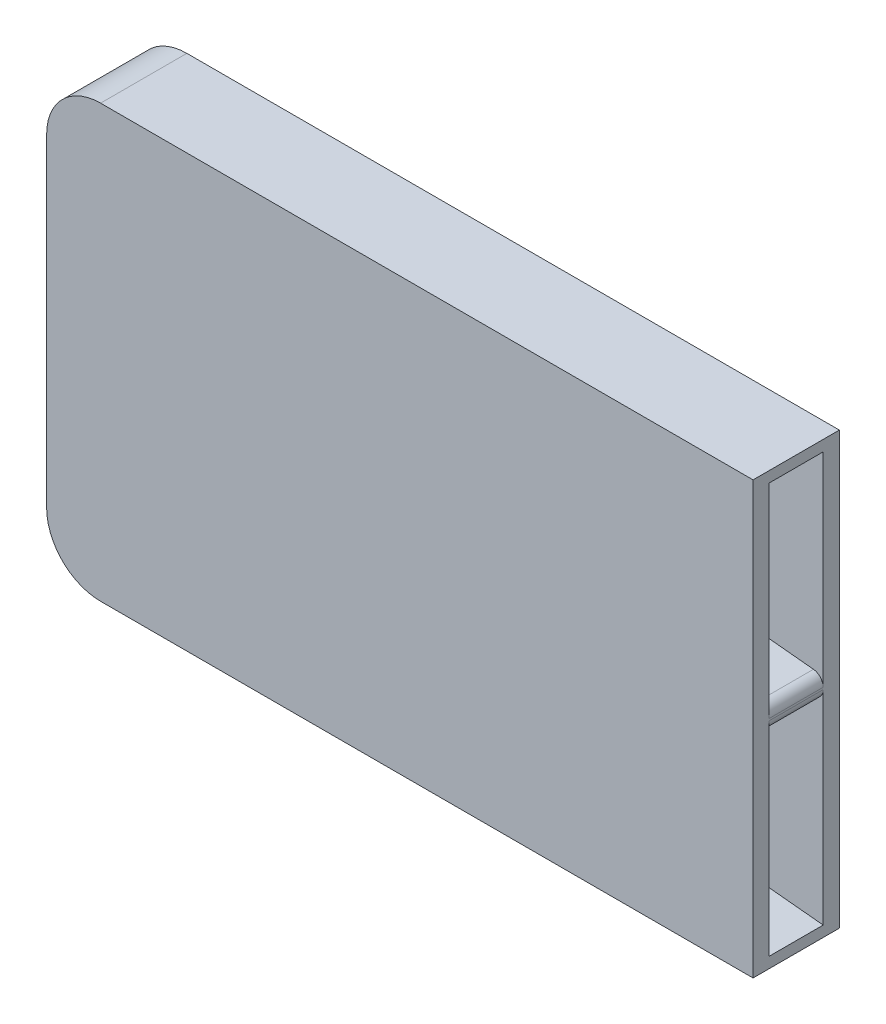
SolidWorks part; units mm, degrees
material "ABS"
ref_plane "Front Plane" through (0, 0, 0) normal (0, 0, 1) x (1, 0, 0)
ref_plane "Top Plane" through (0, 0, 0) normal (0, 1, 0) x (1, 0, 0)
ref_plane "Right Plane" through (0, 0, 0) normal (1, 0, 0) x (0, 0, -1)
sketch "Sketch1" plane through (0, 0, 0) normal (0, 0, 1) x (1, 0, 0)
  line L0 (0, 0) -> (0, 40)
  line L1 (0, 40) -> (65.5, 40)
  line L2 (65.5, 40) -> (65.5, 0)
  line L3 (65.5, 0) -> (0, 0)
  line L4 (65.5, 20) -> (0, 20) construction
  line L5 (0, 7.5) -> (65.5, 1)
  line L6 (0, 12.5) -> (65.5, 19)
  line L7 (0, 10) -> (65.5, 10) construction
  line L8 (0, 32.5) -> (65.5, 39)
  line L9 (0, 30) -> (65.5, 30) construction
  line L10 (0, 27.5) -> (65.5, 21)
  dimension "D1" = 40
  dimension "D2" = 5
  dimension "D3" = 18
  dimension "D4" = 20
  dimension "D5" = 65.5
extrude "Boss-Extrude1" add sketch "Sketch1" against normal blind 1.5 contours L0 L8 L2 L1 | L0 L10 L2 L8 | L10 L0 L6 L2 | L6 L0 L5 L2 | L5 L0 L3 L2 region at (24.402, 2.5392, 0) region at (38.9203, 10, 0) region at (24.402, 20, 0) region at (38.9203, 30, 0) region at (24.402, 37.4608, 0)
extrude "Boss-Extrude2" add sketch "Sketch1<3>" along normal blind 5 contours L0 L8 L2 L1 | L10 L0 L6 L2 | L5 L0 L3 L2 region at (24.402, 2.5392, 0) region at (24.402, 20, 0) region at (24.402, 37.4608, 0)
sketch "Sketch1<3>" plane through (0, 0, 0) normal (0, 0, 1) x (1, 0, 0) same geometry as "Sketch1"
extrude "Boss-Extrude3" add sketch "Sketch1<5>" along normal blind 1.5 from offset 5 contours L0 L8 L2 L1 | L0 L10 L2 L8 | L10 L0 L6 L2 | L6 L0 L5 L2 | L5 L0 L3 L2 region at (24.402, 2.5392, 0) region at (38.9203, 10, 0) region at (24.402, 20, 0) region at (38.9203, 30, 0) region at (24.402, 37.4608, 0)
sketch "Sketch1<5>" plane through (0, 0, 0) normal (0, 0, 1) x (1, 0, 0) same geometry as "Sketch1"
fillet "Fillet1" radius 5 2 edges at (0, 40, 2.5) (0, 0, 2.5)
fillet "Fillet2" radius 1 2 edges at (65.5, 21, 2.5) (65.5, 19, 2.5)
